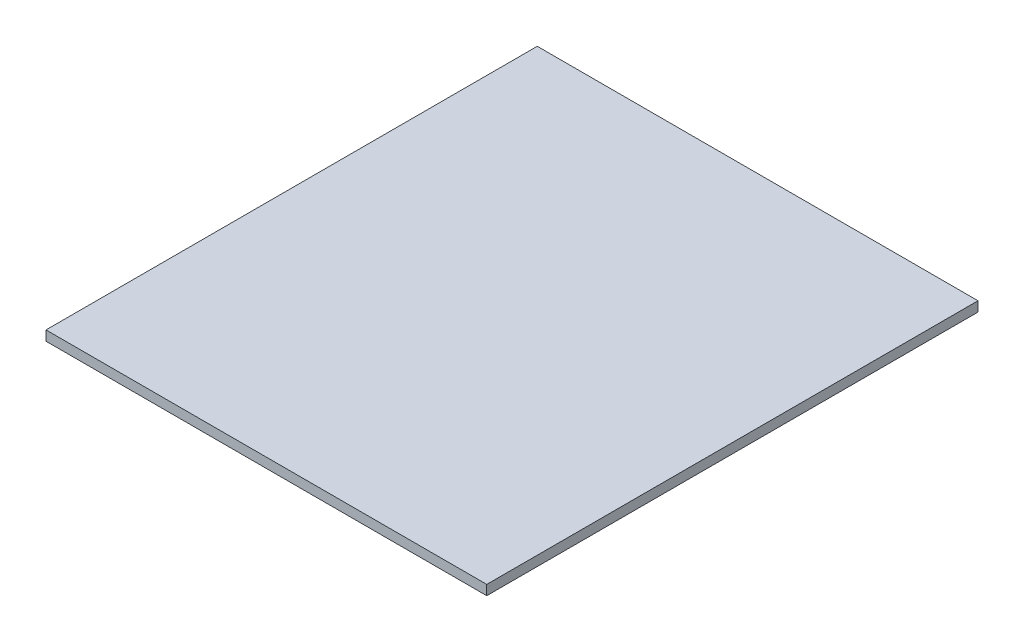
SolidWorks part; units mm, degrees
ref_plane "Front Plane" through (0, 0, 0) normal (0, 0, 1) x (1, 0, 0)
ref_plane "Top Plane" through (0, 0, 0) normal (0, 1, 0) x (1, 0, 0)
ref_plane "Right Plane" through (0, 0, 0) normal (1, 0, 0) x (0, 0, -1)
sketch "Sketch2" plane through (0, 0, 0) normal (0, 0, 1) x (1, 0, 0)
  line L1 (0, 0) -> (134.58, 0)
  line L2 (0, 0) -> (0, -3)
  line L3 (0, -3) -> (134.58, -3)
  line L4 (134.58, 0) -> (134.58, -3)
  dimension "D1" = 3
  dimension "D2" = 134.58
extrude "Boss-Extrude1" add sketch "Sketch2" along normal blind 150
